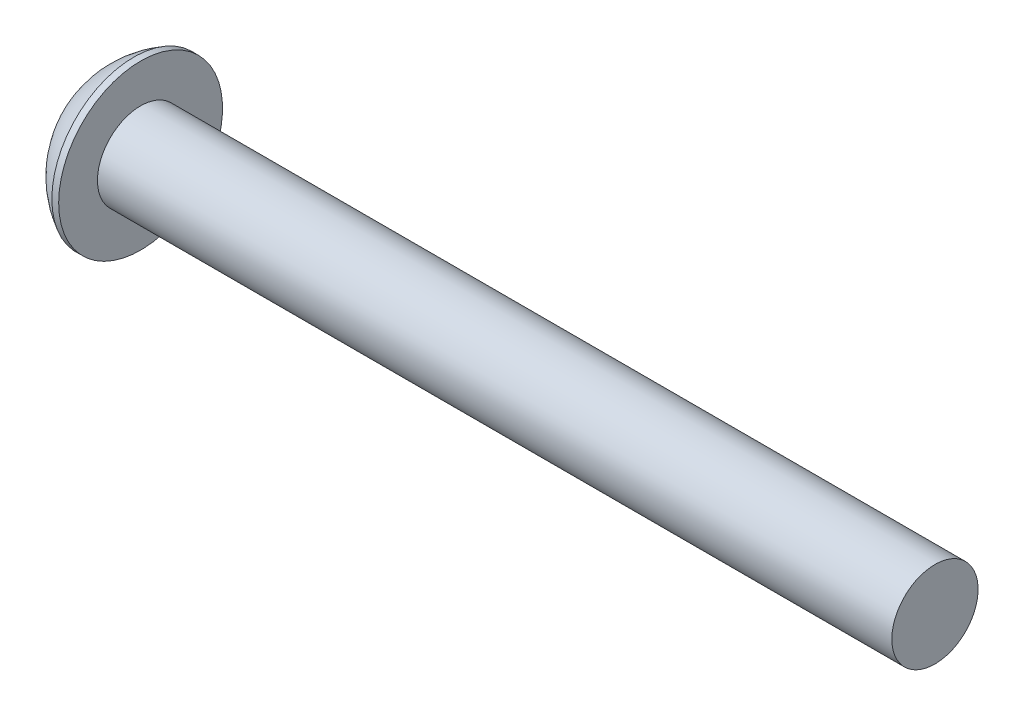
SolidWorks part; units mm, degrees
material "Alloy Steel"
ref_plane "Front" through (0, 0, 0) normal (0, 0, 1) x (1, 0, 0)
ref_plane "Top" through (0, 0, 0) normal (0, 1, 0) x (1, 0, 0)
ref_plane "Right" through (0, 0, 0) normal (1, 0, 0) x (0, 0, -1)
sketch "Sketch1" plane through (0, 0, 0) normal (0, 0, 1) x (1, 0, 0)
  line L0 (0, 0) -> (45.1866, 0)
  line L1 (45.1866, 0) -> (45.1866, 2.413)
  line L2 (45.1866, 2.413) -> (0.7366, 2.413)
  line L3 (0.7366, 2.413) -> (0.7366, 4.5847)
  line L4 (0.7366, 4.5847) -> (0.3556, 4.5847)
  line L5 (-1.8288, 2.413) -> (-1.8288, 1.8288)
  line L6 (0, 0) -> (4.2959, 0) construction
  line L7 (-1.8288, 1.8288) -> (0, 0)
  arc A0 (-1.8288, 2.413) -> (0.3556, 4.5847) centre (2.7515, -0.0097) cw
  dimension "Head Radius" = 5.1816
  dimension "Edge Flat" = 0.381
  dimension "Thread Length" = 44.45
  dimension "Head Diameter" = 9.1694
  dimension "Thread Diameter" = 4.826
  dimension "D6" = 45
  dimension "Head Height" = 2.5654
  dimension "Hex Chamfer Radius" = 1.8288
revolve "Revolve1" add sketch "Sketch1" angle 360 about L6
sketch "Sketch2" plane through (-1.8288, 0, 0) normal (-1, 0, 0) x (0, 0, 1)
  line L1 (1.8331, 0) -> (0.9165, 1.5875)
  line L2 (0.9165, 1.5875) -> (-0.9165, 1.5875)
  line L3 (-0.9165, 1.5875) -> (-1.8331, 0)
  line L4 (-1.8331, 0) -> (-0.9165, -1.5875)
  line L5 (-0.9165, -1.5875) -> (0.9165, -1.5875)
  line L6 (0.9165, -1.5875) -> (1.8331, 0)
  circle A0 centre (0, 0) radius 1.5875 construction
  dimension "Hex Width" = 3.175
extrude "Cut-Extrude1" cut sketch "Sketch2" against normal up to vertex (1.8288 mm away) up to point (0, 0, 0)
other "Freeze***"
